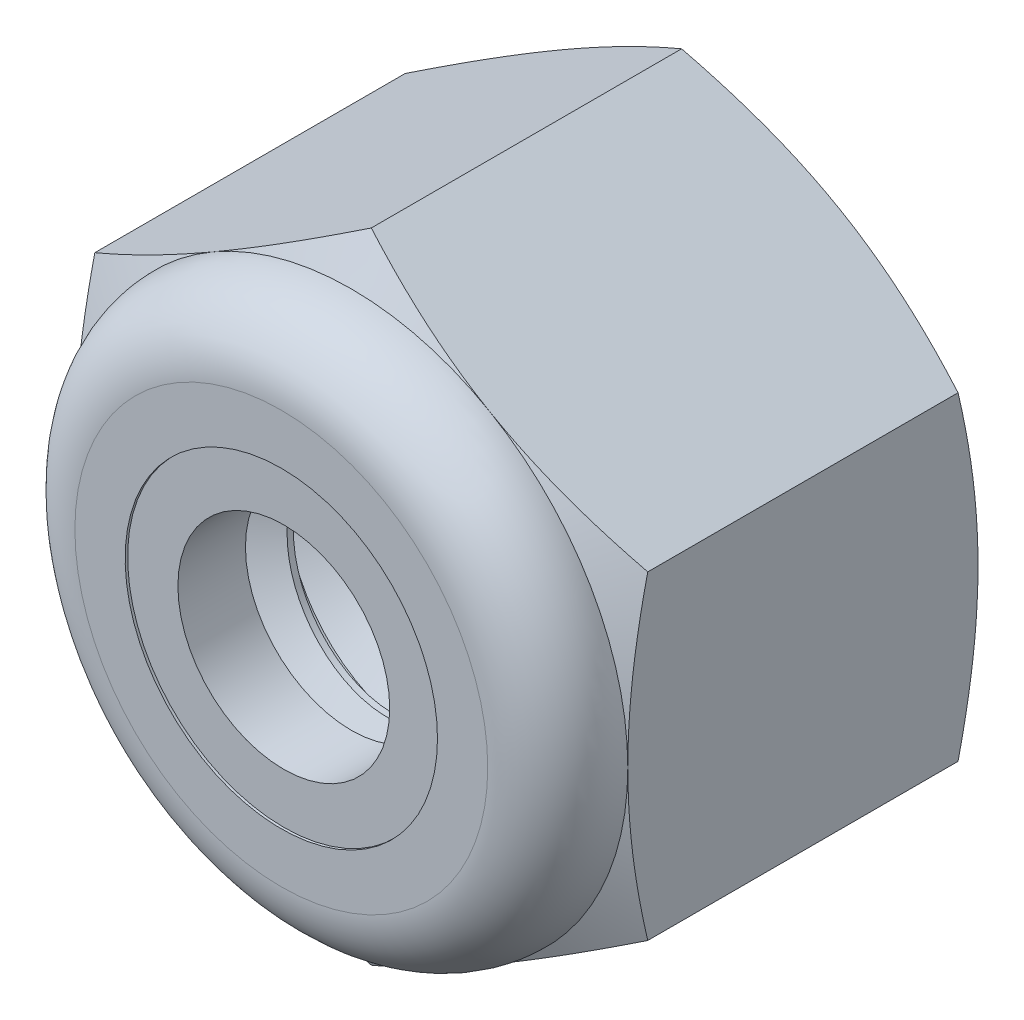
SolidWorks part; units mm, degrees
ref_plane "Front Plane" through (0, 0, 0) normal (0, 0, 1) x (1, 0, 0)
ref_plane "Top Plane" through (0, 0, 0) normal (0, 1, 0) x (1, 0, 0)
ref_plane "Right Plane" through (0, 0, 0) normal (1, 0, 0) x (0, 0, -1)
sketch "Sketch1" plane through (0, 0, 0) normal (0, 0, 1) x (1, 0, 0)
  line L1 (0, 2.8868) -> (-2.5, 1.4434)
  line L2 (-2.5, 1.4434) -> (-2.5, -1.4434)
  line L3 (-2.5, -1.4434) -> (0, -2.8868)
  line L4 (0, -2.8868) -> (2.5, -1.4434)
  line L5 (2.5, -1.4434) -> (2.5, 1.4434)
  line L6 (2.5, 1.4434) -> (0, 2.8868)
  circle A0 centre (0, 0) radius 2.5 construction
  circle A1 centre (0, 0) radius 1.25
  point P10 (0, -1.25)
  point P11 (0, 1.25)
  point P12 (0, 2.5)
  dimension "Thread Size" = 2.5
  dimension "Width" = 5
sketch "Sketch2" plane through (0, 0, 0) normal (1, 0, 0) x (0, 0, -1)
  line L0 (1.9, 0) -> (-1.9, 0) construction
  line L1 (-1.9, 1.25) -> (1.9, 1.25) construction
  line L2 (-1.8775, -1.4122) -> (-3.17, -1.4122) construction
  line L3 (-2.3219, 1.2987) -> (-1.8719, 1.2987) construction
  line L4 (-1.8719, 1.2987) -> (-2.0969, 0.909) construction
  line L5 (-2.0969, 0.909) -> (-2.3219, 1.2987) construction
  line L6 (-2.2938, 1.25) -> (-1.9, 1.25) construction
  line L7 (-2.125, 0.9577) -> (-2.0688, 0.9577) construction
  line L8 (-2.0969, 0.9577) -> (-2.0969, 0.909) construction
  line L9 (-2.0969, 1.25) -> (-2.0969, 1.2987) construction
  line L10 (-1.8859, 1.2744) -> (-2.3078, 1.2744)
  line L11 (-2.3078, 1.2744) -> (-2.125, 0.9577)
  line L12 (-2.125, 0.9577) -> (-2.0688, 0.9577)
  line L13 (-2.0688, 0.9577) -> (-1.8859, 1.2744)
  line L14 (1.9, 0) -> (3.17, 0)
  line L15 (3.17, 0) -> (3.17, 4.1568)
  line L16 (0, 4.1568) -> (0, 2.8868) construction
  line L17 (0, 2.8868) -> (0, 1.4434) construction
  line L18 (1.9, 2.5) -> (-1.2667, 2.5) construction
  line L19 (-2.125, -0.9577) -> (-2.0688, -0.9577) construction
  line L20 (1.9, 2.5) -> (1.9, 0)
  line L21 (1.7197, 2.8868) -> (-1.0863, 2.8868)
  line L22 (1.9, 2.5) -> (1.7197, 2.8868)
  line L23 (-1.9, 0) -> (-1.9, 1.8667) construction
  line L24 (-1.2667, 2.5) -> (-1.0863, 2.8868)
  line L25 (3.17, 4.1568) -> (-3.17, 4.1568)
  line L26 (-1.9, 1.8667) -> (-3.17, 1.8667)
  line L27 (-3.17, 1.8667) -> (-3.17, 4.1568)
  line L28 (-1.8775, 1.8667) -> (-1.8775, 0.9577) construction
  line L29 (-1.8775, 1.4122) -> (-3.17, 1.4122)
  line L30 (-3.17, 1.4122) -> (-3.17, 0)
  line L31 (-3.17, 0) -> (-1.2667, 0)
  line L32 (-1.2667, 0) -> (-1.2667, 2.4775)
  line L33 (-1.8775, 1.4122) -> (-1.8775, 1.8667)
  arc A0 (-1.2667, 2.5) -> (-1.9, 1.8667) centre (-1.2667, 1.8667) ccw
  arc A1 (-1.2667, 2.4775) -> (-1.8775, 1.8667) centre (-1.2667, 1.8667) ccw
  point P4 (0, 0)
  point P18 (-2.0969, 1.2744)
  point P22 (-2.0969, 1.2744)
  point P33 (0, 2.8868)
  point P48 (-3.17, -1.4122)
  point P51 (-2.125, -0.9577)
  dimension "Height" = 3.8
  dimension "Pitch" = 0.45
  dimension "D1" = 0.0563
  dimension "D2" = 1.27
  dimension "D3" = 25
  dimension "D4" = 0.6333
  dimension "D5" = 25
  dimension "D6" = 0.0225
sketch "Sketch3" plane through (0, 0, 0) normal (0, 0, 1) x (1, 0, 0)
  line L0 (0, -2.8868) -> (2.5, -1.4434) construction
  line L1 (2.5, -1.4434) -> (2.5, 1.4434) construction
  line L2 (2.5, 1.4434) -> (0, 2.8868) construction
  line L3 (0, 2.8868) -> (-2.5, 1.4434) construction
  line L4 (-2.5, 1.4434) -> (-2.5, -1.4434) construction
  line L5 (-2.5, -1.4434) -> (0, -2.8868) construction
  line L6 (0, -2.8868) -> (2.5, -1.4434)
  line L7 (2.5, -1.4434) -> (2.5, 1.4434)
  line L8 (2.5, 1.4434) -> (0, 2.8868)
  line L9 (0, 2.8868) -> (-2.5, 1.4434)
  line L10 (-2.5, 1.4434) -> (-2.5, -1.4434)
  line L11 (-2.5, -1.4434) -> (0, -2.8868)
  circle A0 centre (0, 0) radius 1.25 construction
  circle A1 centre (0, 0) radius 1.25
extrude "Boss-Extrude1" add sketch "Sketch3" along normal mid plane 3.8
sketch "Sketch4" plane through (0, 0, 0) normal (1, 0, 0) x (0, 0, -1)
  line L0 (3.17, 4.1568) -> (-3.17, 4.1568) construction
  line L1 (-3.17, 1.8667) -> (-3.17, 4.1568) construction
  line L2 (-1.9, 1.8667) -> (-3.17, 1.8667) construction
  line L3 (-1.2667, 2.5) -> (-1.0863, 2.8868) construction
  line L4 (1.7197, 2.8868) -> (-1.0863, 2.8868) construction
  line L5 (1.9, 2.5) -> (1.7197, 2.8868) construction
  line L6 (1.9, 2.5) -> (1.9, 0) construction
  line L7 (1.9, 0) -> (3.17, 0) construction
  line L8 (3.17, 0) -> (3.17, 4.1568) construction
  line L9 (-3.17, 1.4122) -> (-3.17, 0) construction
  line L10 (-3.17, 0) -> (-1.2667, 0) construction
  line L11 (-1.2667, 0) -> (-1.2667, 2.4775) construction
  line L12 (-1.8775, 1.4122) -> (-1.8775, 1.8667) construction
  line L13 (-1.8775, 1.4122) -> (-3.17, 1.4122) construction
  line L14 (3.17, 4.1568) -> (-3.17, 4.1568)
  line L15 (-3.17, 1.8667) -> (-3.17, 4.1568)
  line L16 (-1.9, 1.8667) -> (-3.17, 1.8667)
  line L17 (-1.2667, 2.5) -> (-1.0863, 2.8868)
  line L18 (1.7197, 2.8868) -> (-1.0863, 2.8868)
  line L19 (1.9, 2.5) -> (1.7197, 2.8868)
  line L20 (1.9, 2.5) -> (1.9, 0)
  line L21 (1.9, 0) -> (3.17, 0)
  line L22 (3.17, 0) -> (3.17, 4.1568)
  line L23 (-3.17, 1.4122) -> (-3.17, 0)
  line L24 (-3.17, 0) -> (-1.2667, 0)
  line L25 (-1.2667, 0) -> (-1.2667, 2.4775)
  line L26 (-1.8775, 1.4122) -> (-1.8775, 1.8667)
  line L27 (-1.8775, 1.4122) -> (-3.17, 1.4122)
  arc A0 (-1.2667, 2.5) -> (-1.9, 1.8667) centre (-1.2667, 1.8667) ccw construction
  arc A1 (-1.2667, 2.4775) -> (-1.8775, 1.8667) centre (-1.2667, 1.8667) ccw construction
  arc A2 (-1.2667, 2.5) -> (-1.9, 1.8667) centre (-1.2667, 1.8667) ccw
  arc A3 (-1.2667, 2.4775) -> (-1.8775, 1.8667) centre (-1.2667, 1.8667) ccw
revolve "Cut-Revolve1" cut sketch "Sketch4" angle 360 about L0
sketch "Sketch5" plane through (0, 0, 0) normal (1, 0, 0) x (0, 0, -1)
  line L0 (-1.8775, 1.8667) -> (-1.8775, 0.9577) construction
  line L1 (-1.2667, 0) -> (-1.2667, 2.4775) construction
  line L2 (-1.8775, 1.8667) -> (-1.8775, 0.9577)
  line L3 (-1.2667, 0.9577) -> (-1.2667, 2.4775)
  line L4 (-1.8775, 0.9577) -> (-1.2667, 0.9577)
  arc A0 (-1.2667, 2.4775) -> (-1.8775, 1.8667) centre (-1.2667, 1.8667) ccw construction
  arc A1 (-1.2667, 2.4775) -> (-1.8775, 1.8667) centre (-1.2667, 1.8667) ccw
revolve "Revolve1" add sketch "Sketch5" angle 360 about L0
sketch "Sketch6" plane through (0, 0, 1.9) normal (0, 0, 1) x (1, 0, 0)
  circle A0 centre (0, 0) radius 1.25 construction
  circle A1 centre (0, 0) radius 1.25
curve "Helix/Spiral1" pitch 0.45 height 4.25 radius 1.25 centre (0, 0, 1.9) axis (0, 0, -1) start towards (0, 1, 0)
sketch "Sketch7" plane through (0, 0, 0) normal (1, 0, 0) x (0, 0, -1)
  line L0 (-2.3078, 1.2744) -> (-2.125, 0.9577) construction
  line L1 (-2.125, 0.9577) -> (-2.0688, 0.9577) construction
  line L2 (-2.0688, 0.9577) -> (-1.8859, 1.2744) construction
  line L3 (-1.8859, 1.2744) -> (-2.3078, 1.2744) construction
  line L4 (-2.3078, 1.2744) -> (-2.125, 0.9577)
  line L5 (-2.125, 0.9577) -> (-2.0688, 0.9577)
  line L6 (-2.0688, 0.9577) -> (-1.8859, 1.2744)
  line L7 (-1.8859, 1.2744) -> (-2.3078, 1.2744)
sweep "Sweep1" add profiles "Sketch7" path "Helix/Spiral1"
sketch "Sketch8" plane through (0, 0, -1.9) normal (0, 0, -1) x (-1, 0, 0)
  circle A2 centre (0, 0) radius 1.2744
  point P2 (0, 1.2744)
extrude "Cut-Extrude1" cut sketch "Sketch8" along normal through all and the other way through all draft 60
sketch "Sketch9" plane through (0, 0, 1.2667) normal (0, 0, 1) x (1, 0, 0)
  circle A2 centre (0, 0) radius 1.2744
  circle A3 centre (0, 0) radius 0.9577 construction
  point P2 (0, 1.2744)
  point P4 (0, 0.9577)
extrude "Cut-Extrude2" cut sketch "Sketch9" along normal through all and the other way through all draft 60
equation "\"D1@Sketch2\" = \"Pitch@Sketch2\" / 8"
equation "\"D4@Sketch2\"=\"Height@Sketch2\"/6"
equation "\"D1@Boss-Extrude1\"=\"Height@Sketch2\""
equation "\"D3@Helix/Spiral1\"=\"Height@Sketch2\"+\"Pitch@Sketch2\""
equation "\"D4@Helix/Spiral1\"=\"Pitch@Sketch2\""
equation "\"D6@Sketch2\"=\"Pitch@Sketch2\"*0.05"
